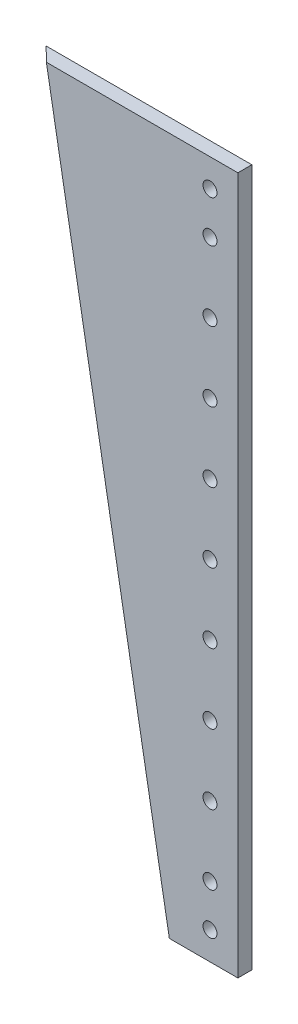
SolidWorks part; units mm, degrees
ref_plane "Front Plane" through (0, 0, 0) normal (0, 0, 1) x (1, 0, 0)
ref_plane "Top Plane" through (0, 0, 0) normal (0, 1, 0) x (1, 0, 0)
ref_plane "Right Plane" through (0, 0, 0) normal (1, 0, 0) x (0, 0, -1)
sketch "Sketch1" plane through (0, 0, 0) normal (0, 0, 1) x (1, 0, 0)
  line L1 (-60, 200) -> (0, 200)
  line L2 (-60, 200) -> (-60, 0)
  line L3 (-60, 0) -> (0, 0)
  line L4 (0, 200) -> (0, 0)
  dimension "D1" = 60
  dimension "D2" = 200
extrude "Boss-Extrude1" add sketch "Sketch1" along normal blind 4
sketch "Sketch6" plane through (0, 0, 0) normal (0, 0, 1) x (1, 0, 0)
  line L0 (-60, 0) -> (0, 0) construction
  line L1 (0, 0) -> (0, 200) construction
  circle A0 centre (-8, 8) radius 2
  circle A1 centre (-8, 20) radius 2
  dimension "D1" = 4
  dimension "D2" = 8
  dimension "D3" = 12
  dimension "D4" = 8
extrude "Cut-Extrude3" cut sketch "Sketch6" along normal up to surface (4 mm away) up to face at (-30, 100, 4)
ref_plane "Plane1" through (0, 100, 0) normal (0, 1, 0) x (1, 0, 0)
mirror "Mirror1" about plane through (0, 100, 0) normal (0, 1, 0) of "Cut-Extrude3"
sketch "Sketch7" plane through (0, 0, 0) normal (0, 0, 1) x (1, 0, 0)
  line L0 (-8, 40) -> (-8, 20) construction
  circle A0 centre (-8, 40) radius 2
  dimension "D2" = 4
  dimension "D1" = 20
extrude "Cut-Extrude4" cut sketch "Sketch7" along normal up to surface (4 mm away) up to face at (-6, 192, 4)
pattern_linear "LPattern1" count 7 spacing 20 along (0, 1, 0) of "Cut-Extrude4"
sketch "Sketch3" plane through (-200, 0, 0) normal (0, 0, -1) x (-1, 0, 0)
  line L8 (-140, 0) -> (-175.2654, 0)
  line L9 (-140, 0) -> (-200, 0) construction
  line L10 (-140, 200) -> (-140, 0) construction
  line L11 (-175.2654, 0) -> (-140, 200)
  line L12 (-140, 200) -> (-140, 0)
  line L13 (-154.1062, 0) -> (-154.1062, 120) construction
  dimension "D1" = 10
  dimension "D2" = 120
  dimension "D3" = 21.1592
extrude "傾斜刀" cut sketch "Sketch3" against normal up to surface (4 mm away) up to face at (-6, 60, 4)
chamfer "傾斜刀倒角" distance 5 angle 45 1 edges at (-42.3673, 100, 4)
chamfer "垂直刀倒角" [suppressed] distance 5 angle 45
